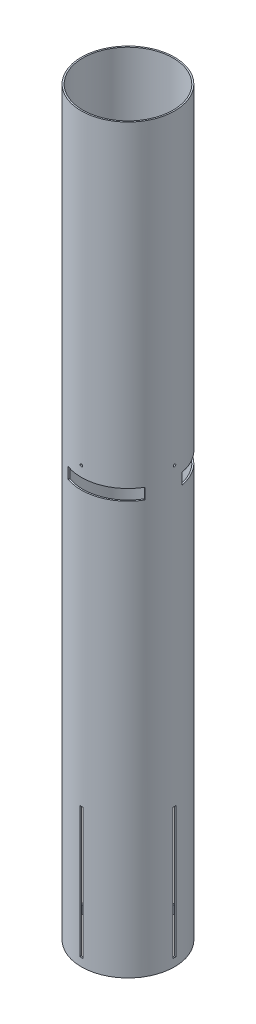
SolidWorks part; units mm, degrees
material "A-Glass Fiber"
ref_plane "Front Plane" through (0, 0, 0) normal (0, 0, 1) x (1, 0, 0)
ref_plane "Top Plane" through (0, 0, 0) normal (0, 1, 0) x (1, 0, 0)
ref_plane "Right Plane" through (0, 0, 0) normal (1, 0, 0) x (0, 0, -1)
sketch "Sketch1" plane through (0, 0, 0) normal (0, 1, 0) x (1, 0, 0)
  circle A0 centre (0, 0) radius 49.53
  circle A1 centre (0, 0) radius 51.1048
  dimension "D1" = 99.06
  dimension "D2" = 102.2096
extrude "Boss-Extrude1" add sketch "Sketch1" along normal blind 812.8
ref_plane "Plane1" through (0, 0, 0) normal (0.7071, 0, 0.7071) x (0.7071, 0, -0.7071)
ref_axis "Axis1" through (0, 812.8, 0) along (0, -1, 0)
sketch "Sketch2" plane through (0, 0, 0) normal (1, 0, 0) x (0, 0, -1)
  line L0 (0, 0) -> (0, 8.89)
  line L1 (1.5875, 8.89) -> (-1.5875, 8.89)
  line L2 (1.5875, 8.89) -> (1.5875, 152.4)
  line L3 (1.5875, 152.4) -> (-1.5875, 152.4)
  line L4 (-1.5875, 8.89) -> (-1.5875, 152.4)
  line L5 (1.5875, 8.89) -> (-1.5875, 152.4) construction
  line L6 (1.5875, 152.4) -> (-1.5875, 8.89) construction
  line L7 (51.1048, 812.8) -> (-51.1048, 812.8) construction
  line L8 (51.1048, 812.8) -> (-51.1048, 812.8)
  line L9 (0, 812.8) -> (0, 476.25)
  line L10 (-51.1048, 0) -> (51.1048, 0) construction
  circle A0 centre (0, 476.25) radius 1.3525
  point P0 (0, 80.645)
  dimension "D4" = 2.7051
  dimension "D1" = 3.175
  dimension "D5" = 476.25
  dimension "D3" = 152.4
  dimension "D2" = 8.89
extrude "Cut-Extrude1" cut sketch "Sketch2" against normal through all contours L4 L1 L2 L3 region at (0, 80.645, 0)
pattern_circular "CirPattern1" count 4 over 360 about axis through (0, 0, 0) along (0, 1, 0) of "Cut-Extrude1" reverse direction yes
extrude "Cut-Extrude2" cut sketch "Sketch2<3>" against normal through all contours A0 region at (0, 475.3207, 0.9293)
sketch "Sketch2<3>" plane through (0, 0, 0) normal (1, 0, 0) x (0, 0, -1) same geometry as "Sketch2"
pattern_circular "CirPattern2" count 4 over 360 about axis through (0, 812.8, 0) along (0, -1, 0) of "Cut-Extrude2"
sketch "Sketch3" plane through (0, 0, 0) normal (0.7071, 0, 0.7071) x (0.7071, 0, -0.7071)
  line L0 (0, 0) -> (0, 127) construction
  circle A0 centre (0, 127) radius 3.175
  dimension "D1" = 6.35
  dimension "D2" = 127
extrude "Cut-Extrude3" cut sketch "Sketch3" against normal through all
ref_plane "Plane3" through (0, 464.82, 0) normal (0, 1, 0) x (1, 0, 0)
sketch "Sketch7" plane through (0, 464.82, 0) normal (0, 1, 0) x (1, 0, 0)
  line L0 (0, 0) -> (-44.2581, -25.5524)
  line L1 (0, 0) -> (0, 93.232) construction
  line L2 (0, 0) -> (-32.8495, 39.1485)
  line L3 (-51.1048, 0) -> (0, 0) construction
  arc A0 (-51.0869, 1.3525) -> (-51.0869, -1.3525) centre (0, 0) ccw construction
  circle A1 centre (0, 0) radius 49.53 construction
  circle A2 centre (0, 0) radius 51.1048
  circle A3 centre (0, 0) radius 51.1048
  circle A4 centre (0, 0) radius 49.53
  circle A5 centre (0, 0) radius 51.1048 construction
  arc A6 (1.3526, 51.0869) -> (-1.3525, 51.0869) centre (0, 0) ccw construction
  arc A7 (-51.0869, 1.3525) -> (-51.0869, -1.3525) centre (0, 0) ccw
  arc A8 (1.3526, 51.0869) -> (-1.3525, 51.0869) centre (0, 0) ccw
  dimension "D1" = 80
  dimension "D3" = 30
  dimension "D2" = 0
extrude "Cut-Extrude4" cut sketch "Sketch7" against normal blind 12.065 contours A4 A3 L0 region at (-43.9137, 464.82, 24.5741)
pattern_circular "CirPattern3" count 3 over 360 about axis through (0, 812.8, 0) along (0, -1, 0) of "Cut-Extrude4"
equation "\"D1@Boss-Extrude1\" = \"Aft_Section_Length\""
equation "\"AB_Coupler_OD_Length\"= 1in"
equation "\"AB_Coupling_Section_Length\"= 0.375in"
equation "\"AB_Coupler_Length\"= \"AB_Coupler_OD_Length\" + \"AB_Coupling_Section_Length\" * 2"
equation "\"AB_Coupler_Num_Screws\"= 4"
equation "\"AB_Coupling_Screw_Diameter\"= 0.1065in"
equation "\"Aft_Section_Length\" = 32in"
equation "\"D4@Sketch2\"=\"AB_Coupling_Screw_Diameter\""
equation "\"D1@CirPattern2\"=\"AB_Coupler_Num_Screws\""
equation "\"Rail_Nut_From_Bottom\"= 5in"
equation "\"Rail_Nut_Diam\"= 0.25in"
equation "\"D1@Sketch3\"=\"Rail_Nut_Diam\""
equation "\"D2@Sketch3\"=\"Rail_Nut_From_Bottom\""
equation "\"AB_BKHD_Thickness\"= 0.375in"
equation "\"AB_Mount_From_Bottom\"= 18.75in"
equation "\"Cutout_Angle\" = 60"
equation "\"Motor_OD\" = 54.4mm"
equation "\"Motor_Length\" = 401mm"
equation "\"Mid_Coupler_Length\" = 12in"
equation "\"AB_Paddle_Height\" = 0.375in"
equation "\"Num_Cutouts\" = 4"
equation "\"AB_Coupler_OD\"= 4.024in"
equation "\"AB_Coupler_ID\"= 3.7in"
equation "\"AB_Coupler_Surface_Diameter\"= 3.899in"
equation "\"AB_Central_Bushing_Length\" = 0.75in"
equation "\"Lead_Screw_Dist\" = 2in"
equation "\"Lead_Screw_Diam\" = 0.375in"
equation "\"Lead_Screw_Length\" = \"Mid_Coupler_Length\" + 2*0.375in + 2*0.5in"
equation "\"Paddle_Pin_Offset\" = 0.25in"
equation "\"Paddle_Pin_Radius\" = 2.25*2/3in"
equation "\"Paddle_Gear_OD\" = 3.2in"
equation "\"Fwd_BKHD_From_Top\" = 18in"
equation "\"Body_Tube_OD\"= 4.024in"
equation "\"Body_Tube_ID\"= 3.90in"
equation "\"Coupler_OD\" = 3.899in"
equation "\"Coupler_ID\" = 3.755in"
equation "\"Fwd_Section_Length\" = 20in"
equation "\"Mid_Section_Length\" = 4in"
equation "\"Aft_Upper_Tube_Length\" = 10in"
equation "\"Aft_Lower_Tube_Length\" = 18in"
equation "\"Nosecone_Coupler_Length\" = 5in"
equation "\"Avionics_Bulkhead_Thickness\" = 0.25in"
equation "\"Avionics_Bulkhead_Lip\" = 0.125in"
equation "\"Avionics_Board_Length\" = \"Mid_Coupler_Length\" - 2*\"Avionics_Bulkhead_Lip\""
equation "\"Lead_Screw_Hole_Diam\" = 0.386in"
equation "\"Centering_Ring_Cutout_Dia\"=1.5in"
equation "\"D2@Sketch1\"=\"Body_Tube_OD\""
equation "\"D1@Sketch1\"=\"Body_Tube_ID\""
equation "\"D5@Sketch2\"=\"AB_Mount_From_Bottom\""
